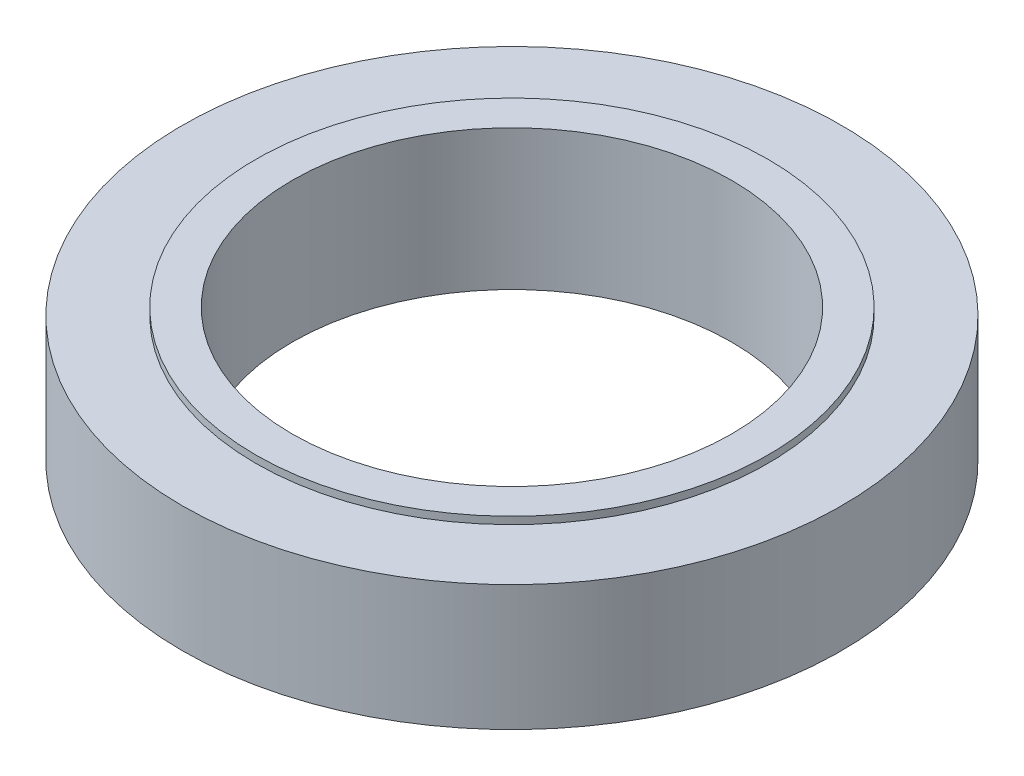
SolidWorks part; units mm, degrees
ref_plane "Front Plane" through (0, 0, 0) normal (0, 0, 1) x (1, 0, 0)
ref_plane "Top Plane" through (0, 0, 0) normal (0, 1, 0) x (1, 0, 0)
ref_plane "Right Plane" through (0, 0, 0) normal (1, 0, 0) x (0, 0, -1)
sketch "Sketch2" plane through (0, 0, 0) normal (0, 1, 0) x (1, 0, 0)
  circle A0 centre (0, 0) radius 16.6687
  circle A1 centre (0, 0) radius 11.1125
  circle A2 centre (0, 0) radius 12.954
  dimension "D1" = 33.3375
  dimension "D2" = 22.225
  dimension "D3" = 25.908
extrude "Boss-Extrude1" add sketch "Sketch2" along normal mid plane 6.35 contours A0 A2 | A2 A1 region at (-16.1973, 0, 0) region at (-12.5876, 0, 0)
extrude "Boss-Extrude2" add sketch "Sketch2<3>" along normal mid plane 7.0866 contours A2 A1 region at (-12.5876, 0, 0)
sketch "Sketch2<3>" plane through (0, 0, 0) normal (0, 1, 0) x (1, 0, 0) same geometry as "Sketch2"
